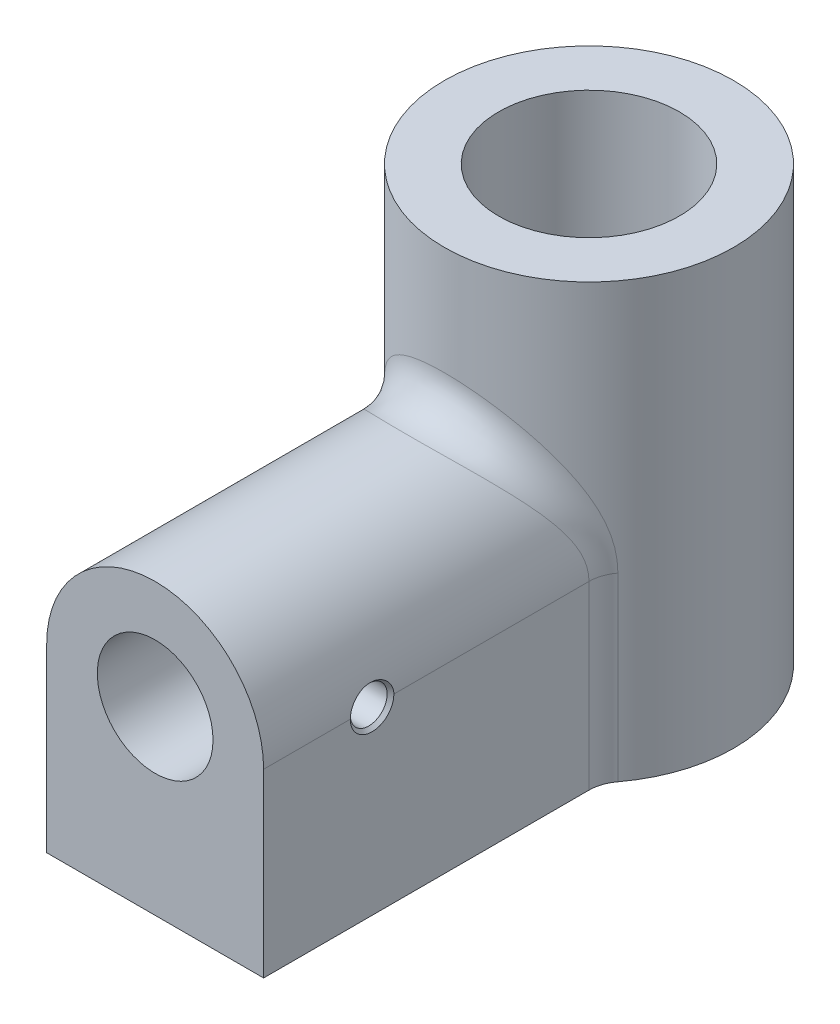
SolidWorks part; units mm, degrees
ref_plane "前视基准面" through (0, 0, 0) normal (0, 0, 1) x (1, 0, 0)
ref_plane "上视基准面" through (0, 0, 0) normal (0, 1, 0) x (1, 0, 0)
ref_plane "右视基准面" through (0, 0, 0) normal (1, 0, 0) x (0, 0, -1)
other "Configuration Table"
sketch "草图3" plane through (0, 0, 0) normal (0, 0, 1) x (1, 0, 0)
  line L0 (0, 0) -> (60, 0)
  line L1 (60, 0) -> (60, 50)
  line L2 (0, 50) -> (0, 0)
  arc A0 (60, 50) -> (0, 50) centre (30, 50) ccw
  circle A1 centre (30, 50) radius 16
  dimension "D3" = 32
  dimension "D1" = 50
  dimension "D2" = 60
extrude "凸台-拉伸2" add sketch "草图3" along normal blind 104 contours A1 | L2 L0 L1 A0
sketch "草图4" plane through (0, 0, 0) normal (0, -1, 0) x (1, 0, 0)
  line L0 (30, -7.3886) -> (30, 7.3886)
  line L3 (0, 104) -> (60, 104) construction
  circle A0 centre (30, -16) radius 25
  circle A1 centre (30, -16) radius 40
  point P3 (30, 0)
  line M2 (0, 0) -> (60, 0)
  line M3 (60, 0) -> (60, 104)
  line M5 (0, 104) -> (0, 0)
  dimension "D1" = 80
  dimension "D2" = 50
  dimension "D3" = 120
extrude "凸台-拉伸3" add sketch "草图4" against normal blind 120 contours A1 A0 M3 M5 M2 | A1 A0 M5 M3 M2 region at (54.4858, 0, -7.1383) region at (30, 0, 11.9857)
extrude "切除-拉伸1" cut sketch "草图4<3>" against normal through all both and the other way through all contours A0 M2 | A0 M2 region at (30, 0, -18.7424) region at (39.6047, 0, 0.3946)
sketch "草图4<3>" plane through (0, 0, 0) normal (0, -1, 0) x (1, 0, 0) same geometry as "草图4"
sketch "草图6" plane through (0, 0, 104) normal (0, 0, 1) x (1, 0, 0)
  circle A0 centre (30, 50) radius 16 construction
  circle A1 centre (30, 50) radius 16
extrude "切除-拉伸6" cut sketch "草图6" against normal up to next
fillet "圆角1" radius 10 3 edges at (0, 25, 10.4575) (31.783, 79.947, 23.9602) (60, 25, 10.4575)
sketch "草图10" plane through (60, 0, 0) normal (1, 0, 0) x (0, 0, -1)
  line L0 (-104, 50) -> (-14, 50) construction
  line L1 (-104, 0) -> (-104, 50) construction
  point P0 (-74, 50)
  point P5 (-74, 50)
  dimension "D1" = 30
hole_wizard "M12 螺纹孔1" positions "草图10" profile "草图11" tap size "M12" standard "GB"
sketch "草图11" plane through (60, 50, 74) normal (0, 1, 0) x (0, 0, -1)
  line L0 (0, 0) -> (0, 33.0644)
  line L1 (0, 33.0644) -> (5.1, 30)
  line L2 (5.1, 30) -> (5.1, 0.925)
  line L3 (5.1, 0.925) -> (6.025, 0)
  line L5 (6.025, 0) -> (0, 0)
  line L6 (-5.1, 0.925) -> (-6.025, 0) construction
  line L10 (0, 33.0644) -> (-5.1, 30) construction
  line L11 (0, -6.35) -> (0, 107.95) construction
  dimension "螺纹孔钻头直径" = 10.2
  dimension "螺纹孔钻头深度" = 30
  dimension "近端锥形沉头孔直径" = 12.05
  dimension "近端锥形沉头孔角度" = 90
  dimension "导头角度" = 118
